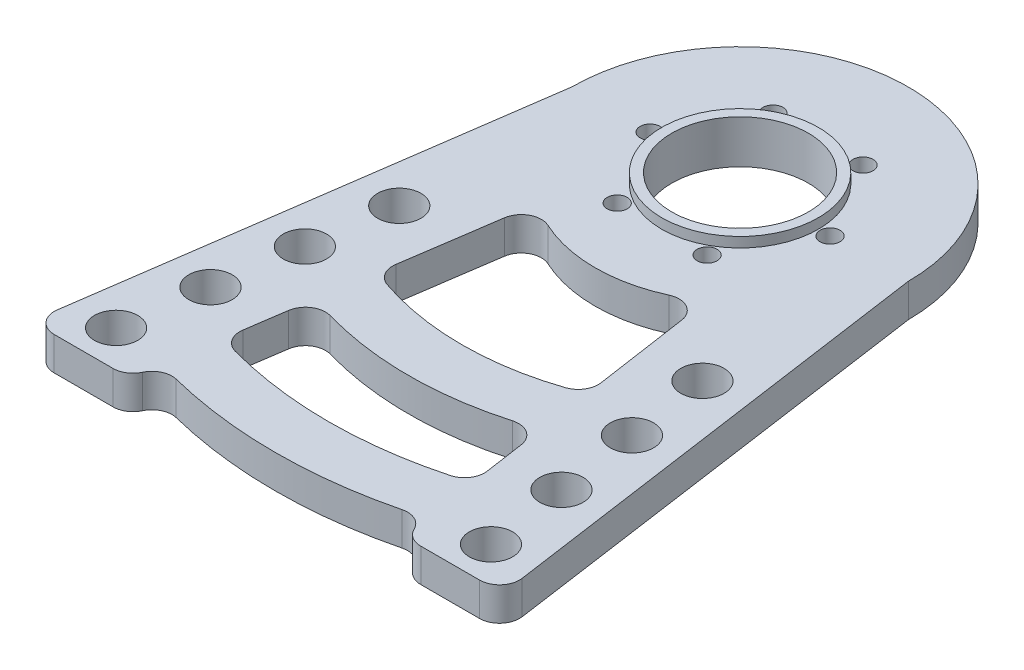
SolidWorks part; units mm, degrees
ref_plane "Front Plane" through (0, 0, 0) normal (0, 0, 1) x (1, 0, 0)
ref_plane "Top Plane" through (0, 0, 0) normal (0, 1, 0) x (1, 0, 0)
ref_plane "Right Plane" through (0, 0, 0) normal (1, 0, 0) x (0, 0, -1)
sketch "Sketch1" plane through (0, 0, 0) normal (0, 1, 0) x (1, 0, 0)
  line L0 (0, 0) -> (33, 0) construction
  line L1 (0, 0) -> (0, 29) construction
  line L6 (39.5, 0) -> (25.25, 100)
  line L7 (-39.5, 0) -> (-25.25, 100)
  line L8 (0, 89.75) -> (0, 100) construction
  arc A0 (-39.5, 0) -> (39.5, 0) centre (0, 0) ccw
  circle A1 centre (0, 0) radius 29
  circle A3 centre (33, 0) radius 2.25
  circle A4 centre (16.5, -28.5788) radius 2.25
  circle A5 centre (-16.5, -28.5788) radius 2.25
  circle A6 centre (-33, 0) radius 2.25
  circle A10 centre (0, 100) radius 10.25
  arc A11 (25.25, 100) -> (-25.25, 100) centre (0, 100) ccw
  circle A12 centre (-16.5, 28.5788) radius 2.25 [skipped]
  circle A13 centre (16.5, 28.5788) radius 2.25 [skipped]
  point P19 (0, 0)
  dimension "D1" = 79
  dimension "D2" = 58
  dimension "D4" = 4.5
  dimension "D7" = 20.5
  dimension "D8" = 15
  dimension "D3" = 33
  dimension "D6" = 100
  dimension "D5" = 6
extrude "Boss-Extrude1" add sketch "Sketch1" along normal blind 5
ref_axis "Axis1" through (0, 5, 0) along (0, -1, 0)
sketch "Sketch3" plane through (0, 5, 0) normal (0, 1, 0) x (1, 0, 0)
  line L0 (0, 0) -> (0, 100) construction
sketch "Sketch4" plane through (0, 5, 0) normal (0, 1, 0) x (1, 0, 0)
  circle A0 centre (0, 100) radius 10.25
  circle A1 centre (0, 100) radius 11.75
  dimension "D1" = 1.5
  dimension "D2" = 20.5
extrude "Boss-Extrude2" add sketch "Sketch4" along normal blind 1.5
sketch "Sketch12" plane through (0, 5, 0) normal (0, 1, 0) x (1, 0, 0)
  line L0 (31.8681, 53.985) -> (28.2815, 78.7264)
  line L1 (39.5, 0) -> (25.25, 100) construction
  line L2 (31.8681, 53.985) -> (35.4547, 29.2436)
  line L3 (35.4547, 29.2436) -> (22.5891, 27.3786)
  line L4 (22.5891, 27.3786) -> (15.416, 76.8614)
  line L5 (15.416, 76.8614) -> (28.2815, 78.7264)
  line L6 (22.7454, 71.6085) -> (21.8487, 77.7939) construction
  line L7 (31.8681, 53.985) -> (19.0026, 52.12) construction
  line L8 (25.4353, 53.0525) -> (24.5387, 59.2378) construction
  circle A0 centre (22.7454, 71.6085) radius 3.25
  circle A1 centre (24.5387, 59.2378) radius 3.25
  circle A2 centre (28.1253, 34.4965) radius 3.25
  circle A3 centre (26.332, 46.8671) radius 3.25
  dimension "D3" = 6.5
  dimension "D1" = 25
  dimension "D2" = 13
  dimension "D4" = 6.25
extrude "Cut-Extrude5" cut sketch "Sketch12" against normal up to surface (5 mm away) contours A2 | A3 | A1 | A0 region at (22.7454, 5, -71.6085) region at (24.5387, 5, -59.2378) region at (28.1253, 5, -34.4965) region at (26.332, 5, -46.8671) up to face at (0, 0, -46.4375)
mirror "Mirror1" about plane through (0, 0, 0) normal (1, 0, 0) of "Cut-Extrude5"
sketch "Sketch13" plane through (0, 5, 0) normal (0, 1, 0) x (1, 0, 0)
  line L1 (59.3176, 29) -> (-59.3176, 29)
  line L3 (59.3176, -47.2365) -> (-59.3176, -47.2365)
  line L4 (-59.3176, 29) -> (-59.3176, -47.2365)
  line L5 (59.3176, 29) -> (59.3176, -47.2365)
extrude "Cut-Extrude6" cut sketch "Sketch13" against normal up to surface (5 mm away) up to face at (-26.332, 0, -43.6171)
sketch "Sketch14" plane through (0, 5, 0) normal (0, 1, 0) x (1, 0, 0)
  line L3 (35.3675, 29) -> (-35.3675, 29) construction
  line L9 (-20.5006, 29) -> (20.5006, 29)
  line L10 (20.5006, 29) -> (12.6546, 82.3104)
  line L11 (-12.6546, 82.3104) -> (-20.5006, 29)
  circle A2 centre (0, 100) radius 21.75
  arc A3 (-12.6546, 82.3104) -> (12.6546, 82.3104) centre (0, 100) ccw
  dimension "D1" = 10
extrude "Cut-Extrude7" cut sketch "Sketch14" against normal up to surface (5 mm away) up to face at (-26.332, 0, -43.6171)
fillet "Fillet2" radius 3 6 edges at (35.3675, 2.5, -29) (20.5006, 2.5, -29) (-35.3675, 2.5, -29) (-20.5006, 2.5, -29) (12.6546, 2.5, -82.3104) (-12.6546, 2.5, -82.3104)
sketch "Sketch15" plane through (0, 0, 0) normal (0, -1, 0) x (1, 0, 0)
  line L0 (0, -100) -> (13.5, -100) construction
  circle A0 centre (13.5, -100) radius 1.5
  dimension "D2" = 3
  dimension "D1" = 13.5
extrude "Cut-Extrude8" cut sketch "Sketch15" against normal blind 10
pattern_circular "CirPattern1" count 6 every 60 about axis through (0, 5, -100) along (0, -1, 0) of "Cut-Extrude8"
sketch "Sketch16" plane through (0, 5, 0) normal (0, 1, 0) x (1, 0, 0)
  line L0 (20.1234, 31.5632) -> (13.2971, 77.9452) construction
  line L1 (-13.2971, 77.9452) -> (-20.1234, 31.5632) construction
  line L2 (19.8904, 33.1462) -> (18.712, 41.1534)
  line L3 (-15.7422, 61.3316) -> (-16.9358, 53.2214)
  line L4 (16.9358, 53.2214) -> (15.7422, 61.3316)
  line L5 (-18.712, 41.1534) -> (-19.8904, 33.1462)
  line L6 (23.0914, 29) -> (31.9097, 29)
  line L7 (34.8797, 32.4232) -> (25.25, 100)
  line L8 (-25.25, 100) -> (-34.8797, 32.4232)
  line L9 (-31.9097, 29) -> (-23.0914, 29)
  line L10 (-20.1234, 31.5632) -> (-13.2971, 77.9452)
  line L11 (13.2971, 77.9452) -> (20.1234, 31.5632)
  line L16 (-16.9358, 53.2214) -> (-15.7422, 61.3316)
  line L17 (15.7422, 61.3316) -> (16.9358, 53.2214)
  circle A0 centre (0, 100) radius 69.75 construction
  arc A1 (-16.9358, 53.2214) -> (16.9358, 53.2214) centre (0, 100) ccw
  circle A2 centre (0, 100) radius 41.75
  arc A3 (-15.7422, 61.3316) -> (15.7422, 61.3316) centre (0, 100) ccw
  circle A4 centre (0, 100) radius 49.75 construction
  circle A5 centre (0, 100) radius 41.75 construction
  arc A6 (-19.8904, 33.1462) -> (19.8904, 33.1462) centre (0, 100) ccw
  circle A7 centre (0, 100) radius 61.75
  arc A8 (-18.712, 41.1534) -> (18.712, 41.1534) centre (0, 100) ccw
  circle A9 centre (0, 100) radius 61.75 construction
  arc A13 (25.25, 100) -> (-25.25, 100) centre (0, 100) ccw
  arc A14 (31.9097, 29) -> (34.8797, 32.4232) centre (31.9097, 32) ccw
  arc A15 (-34.8797, 32.4232) -> (-31.9097, 29) centre (-31.9097, 32) ccw
  arc A16 (-23.0914, 29) -> (-20.1234, 31.5632) centre (-23.0914, 32) ccw
  arc A17 (-9.0771, 80.2346) -> (9.0771, 80.2346) centre (0, 100) ccw
  arc A18 (-9.0771, 80.2346) -> (-13.2971, 77.9452) centre (-10.3291, 77.5084) ccw
  arc A19 (13.2971, 77.9452) -> (9.0771, 80.2346) centre (10.3291, 77.5084) ccw
  arc A28 (20.1234, 31.5632) -> (23.0914, 29) centre (23.0914, 32) ccw
  line M31 (-20.1234, 31.5632) -> (-13.2971, 77.9452)
  line M35 (13.2971, 77.9452) -> (20.1234, 31.5632)
  dimension "D1" = 30
  dimension "D2" = 8
  dimension "D3" = 0
  dimension "D4" = 50
  dimension "D5" = 8
extrude "Boss-Extrude3" add sketch "Sketch16" against normal up to surface (5 mm away) contours A8 A6 M31 M35 | A3 A1 M31 M35 region at (0, 5, -35.1794) region at (0, 5, -55.2157) up to face at (8.049, 0, -89.0587)
fillet "Fillet3" radius 3 8 edges at (-15.7422, 2.5, -61.3316) (15.7422, 2.5, -61.3316) (16.9358, 2.5, -53.2214) (18.712, 2.5, -41.1534) (-18.712, 2.5, -41.1534) (19.8904, 2.5, -33.1462) (-16.9358, 2.5, -53.2214) (-19.8904, 2.5, -33.1462)
